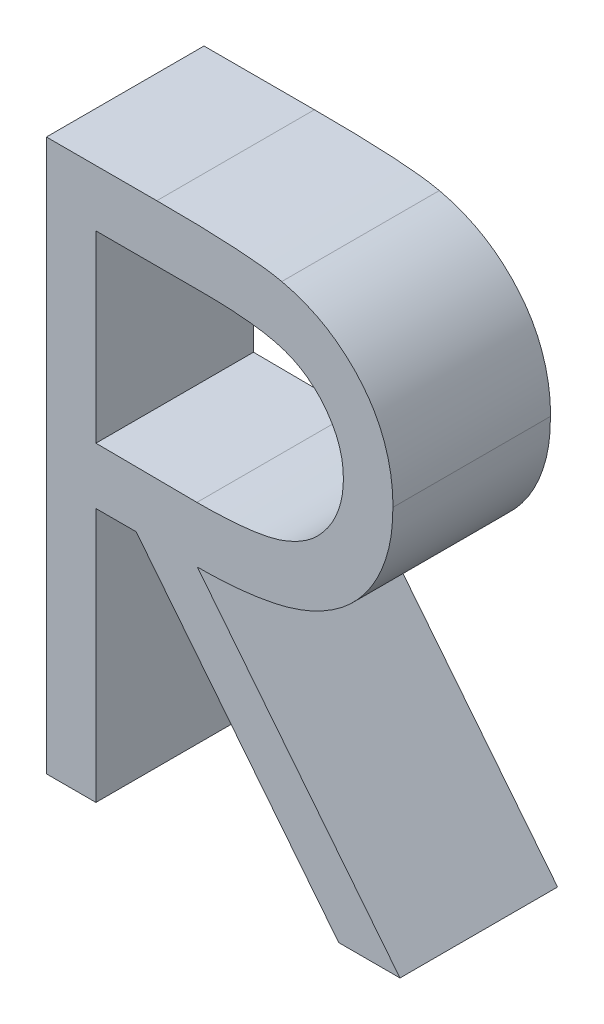
SolidWorks part; units mm, degrees
ref_plane "Front Plane" through (0, 0, 0) normal (0, 0, 1) x (1, 0, 0)
ref_plane "Top Plane" through (0, 0, 0) normal (0, 1, 0) x (1, 0, 0)
ref_plane "Right Plane" through (0, 0, 0) normal (1, 0, 0) x (0, 0, -1)
sketch "Sketch1" plane through (0, 0, 0) normal (0, 0, 1) x (1, 0, 0)
  text T0 "R"
extrude "Boss-Extrude1" add sketch "Sketch1" along normal blind 1
